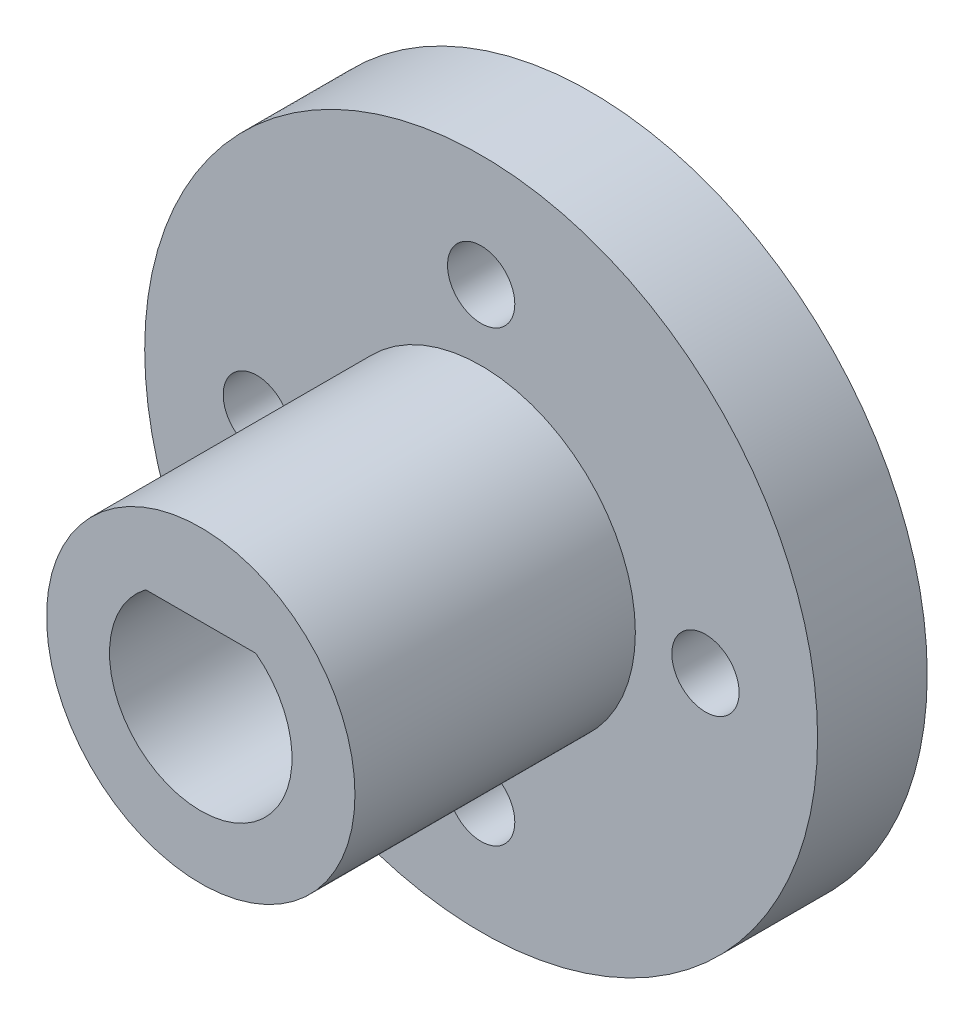
SolidWorks part; units mm, degrees
ref_plane "Plan de face" through (0, 0, 0) normal (0, 0, 1) x (1, 0, 0)
ref_plane "Plan de dessus" through (0, 0, 0) normal (0, 1, 0) x (1, 0, 0)
ref_plane "Plan de droite" through (0, 0, 0) normal (1, 0, 0) x (0, 0, -1)
sketch "Esquisse1" plane through (0, 0, 0) normal (0, 0, 1) x (1, 0, 0)
  circle A0 centre (0, 0) radius 12
  dimension "D1" = 24
extrude "Boss.-Extru.1" add sketch "Esquisse1" along normal blind 3.91
sketch "Esquisse6" plane through (0, 0, 0) normal (0, 0, -1) x (-1, 0, 0)
  circle A0 centre (0, 0) radius 4.15
  dimension "D1" = 8.3
extrude "Enlèv. mat.-Extru.2" cut sketch "Esquisse6" against normal blind 2.5
sketch "Esquisse7" plane through (0, 0, 3.91) normal (0, 0, 1) x (1, 0, 0)
  line L0 (1.9649, 2.595) -> (-1.9649, 2.595)
  line L1 (-5.4714, -3.255) -> (6.192, -3.255) construction
  arc A0 (-1.9649, 2.595) -> (1.9649, 2.595) centre (0, 0) ccw
  circle A1 centre (0, 0) radius 5.5
  dimension "D1" = 6.51
  dimension "D3" = 11
  dimension "D2" = 5.85
extrude "Boss.-Extru.2" add sketch "Esquisse7" along normal blind 10 contours A1 L1 A0 L0 | L1 A1 region at (-2.2167, -3.1144, 3.91) region at (0, -4.1708, 3.91)
hole_wizard "Dégagement M21" positions "Esquisse10" profile "Esquisse11" hole size "M2" standard "Ansi Metric" end condition through all
sketch "Esquisse10" plane through (0, 0, 3.91) normal (0, 0, 1) x (1, 0, 0)
  point P0 (0, 8)
  dimension "D1" = 8
sketch "Esquisse11" plane through (0, 8, 3.91) normal (1, 0, 0) x (0, -1, 0)
  line L0 (0, 0) -> (0, 3.91)
  line L1 (0, 3.91) -> (1.2, 3.91)
  line L2 (1.2, 3.91) -> (1.2, 0)
  line L5 (1.2, 0) -> (0, 0)
  line L11 (0, -6.35) -> (0, 107.95) construction
  dimension "Diamètre du perçage jusqu'au prochain" = 2.4
  dimension "Profondeur du perçage jusqu'au prochain" = 3.91
pattern_circular "Répétition circulaire2" count 4 every 90 about axis through (0, 0, 3.91) along (0, 0, 1) of "Dégagement M21"
